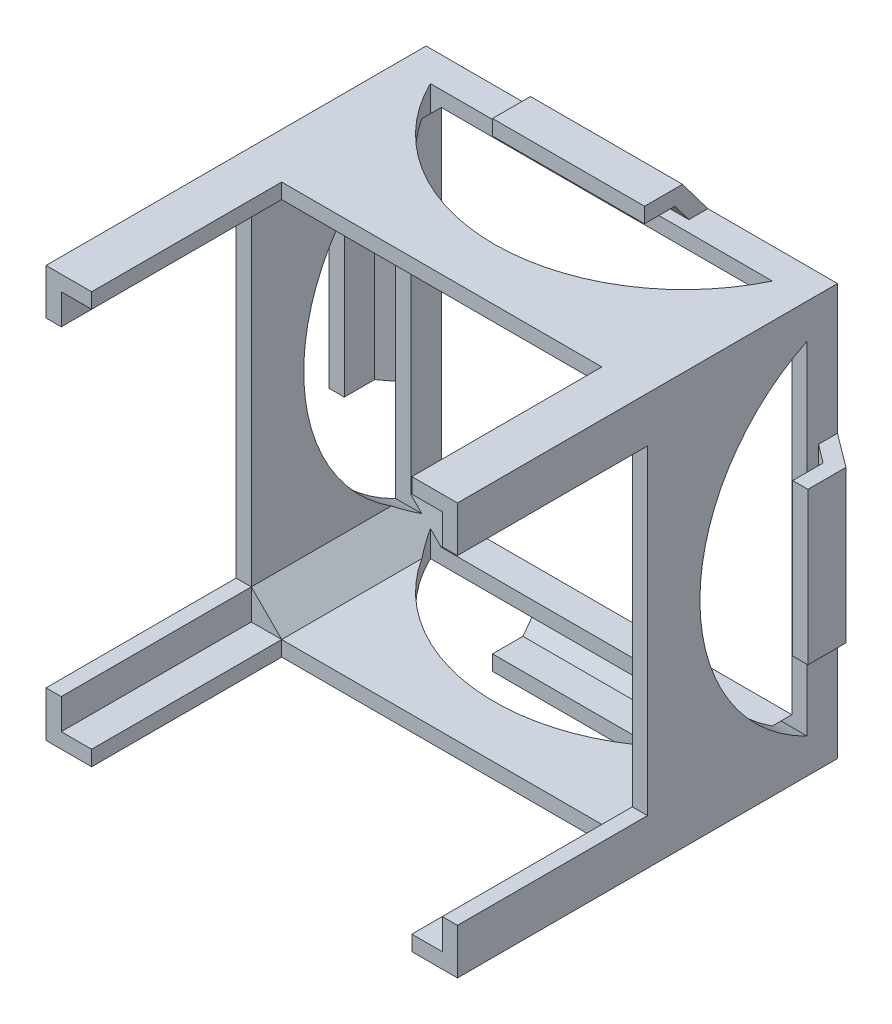
SolidWorks part; units mm, degrees
ref_plane "Front Plane" through (0, 0, 0) normal (0, 0, 1) x (1, 0, 0)
ref_plane "Top Plane" through (0, 0, 0) normal (0, 1, 0) x (1, 0, 0)
ref_plane "Right Plane" through (0, 0, 0) normal (1, 0, 0) x (0, 0, -1)
sketch "Sketch1" plane through (0, 0, 0) normal (0, 0, 1) x (1, 0, 0)
  line L1 (-50.125, -50.125) -> (50.125, -50.125)
  line L2 (-50.125, -50.125) -> (-50.125, 50.125)
  line L3 (-50.125, 50.125) -> (50.125, 50.125)
  line L4 (50.125, -50.125) -> (50.125, 50.125)
  line L5 (-50.125, -50.125) -> (50.125, 50.125) construction
  line L6 (-50.125, 50.125) -> (50.125, -50.125) construction
  line L7 (-54.125, -54.125) -> (54.125, -54.125)
  line L8 (-54.125, -54.125) -> (-54.125, 54.125)
  line L9 (-54.125, 54.125) -> (54.125, 54.125)
  line L10 (54.125, -54.125) -> (54.125, 54.125)
  line L11 (-54.125, -54.125) -> (54.125, 54.125) construction
  line L12 (-54.125, 54.125) -> (54.125, -54.125) construction
  point P0 (0, 0)
  point P6 (0, 0)
  dimension "D1" = 100.25
  dimension "D2" = 4
extrude "Base" add sketch "Sketch1" along normal blind 50
chamfer "Chamfer" distance 8 angle 45 4 edges at (-50.125, -50.125, 25) (50.125, -50.125, 25) (50.125, 50.125, 25) (-50.125, 50.125, 25)
sketch "Sketch3" plane through (0, 0, 0) normal (0, 1, 0) x (1, 0, 0)
  line L0 (54.125, 0) -> (63, -6.6563)
  line L1 (54.125, -50) -> (54.125, 0) construction
  line L2 (63, -6.6563) -> (63, -16.6562)
  line L3 (63, -16.6562) -> (59, -16.6562)
  line L4 (59, -16.6562) -> (59, -8.6562)
  line L5 (59, -8.6562) -> (54.125, -5)
  line L6 (59, -8.6562) -> (61.4, -5.4563) construction
  line L7 (54.125, -5) -> (54.125, 0)
  dimension "D4" = 63
  dimension "D3" = 10
extrude "Wall-Brace" add sketch "Sketch3" along normal blind 20 and the other way blind 20
ref_axis "Vertical-Axis" through (0, 0, -5) along (0, 0, 1)
pattern_circular "Wall-Brace-Pattern" count 4 over 360 about axis through (0, 0, -5) along (0, 0, 1) of "Wall-Brace"
sketch "Sketch4" plane through (0, 0, 50) normal (0, 0, 1) x (1, 0, 0)
  line L0 (-50.125, 42.125) -> (-54.125, 42.125)
  line L1 (-54.125, 54.125) -> (-54.125, -54.125) construction
  line L2 (-54.125, 42.125) -> (-54.125, 54.125)
  line L3 (-54.125, 54.125) -> (-42.125, 54.125)
  line L4 (54.125, 54.125) -> (-54.125, 54.125) construction
  line L5 (-42.125, 54.125) -> (-42.125, 50.125)
  line L6 (-42.125, 50.125) -> (-50.125, 50.125)
  line L7 (-50.125, 50.125) -> (-50.125, 42.125)
extrude "Lattice-Support-Arm" add sketch "Sketch4" along normal blind 50
mirror "Lattice-Support-Arm-Mirror" about plane through (0, 0, 0) normal (1, 0, 0) of "Lattice-Support-Arm" second plane through (0, 0, 0) second plane normal (0, 1, 0)
sketch "Sketch5" plane through (54.125, 0, 0) normal (-1, 0, 0) x (0, 0, 1)
  line L9 (8, 45) -> (8, -45)
  line L11 (0, 54.125) -> (0, 20) construction
  line L12 (8, -54.125) -> (8, 54.125) construction
  line L14 (100, -54.125) -> (0, -54.125) construction
  line L15 (100, 54.125) -> (0, 54.125) construction
  arc A3 (8, 45) -> (8, -45) centre (-13.7945, 0) cw
  point P13 (8, 0)
  point P16 (8, 0)
  dimension "D2" = 50
  dimension "D1" = 90
  dimension "D3" = 8
extrude "Arches-1" cut sketch "Sketch5" along normal up to surface (108.25 mm away) up to face at (-54.125, 0, 42.5)
sketch "Sketch6" plane through (0, 54.125, 0) normal (0, 1, 0) x (1, 0, 0)
  line L0 (-45, -8) -> (45, -8)
  line L1 (-54.125, -8) -> (54.125, -8) construction
  line L2 (-54.125, -100) -> (-54.125, 0) construction
  line L3 (54.125, -100) -> (54.125, 0) construction
  line L4 (-20, 0) -> (-54.125, 0) construction
  arc A0 (45, -8) -> (-45, -8) centre (0, 13.7945) cw
  point P4 (0, -8)
  point P10 (0, -8)
  dimension "D2" = 50
  dimension "D1" = 90
  dimension "D3" = 8
extrude "Arches-2" cut sketch "Sketch6" against normal up to surface (108.25 mm away) up to face at (0, -54.125, 42.5)
equation "\"D1@Sketch1\" = \"block-base\" + \"block-tolerance\""
equation "\"D2@Sketch1\" = \"frame-thickness\""
equation "\"D1@Chamfer\" = \"frame-thickness\" * 2"
equation "\"D1@Sketch3\" = \"frame-thickness\""
equation "\"D4@Sketch3\"=\"box-size\"/2"
equation "\"D1@Wall-Brace\" = 20mm"
equation "\"D2@Wall-Brace\" = 20mm"
equation "\"box-size\"= 126mm"
equation "\"block-base\"= 100mm"
equation "\"block-height\"= 50mm"
equation "\"hole-separation\"= 50mm"
equation "\"frame-thickness\"= 4mm"
equation "\"block-tolerance\"= 0.25mm"
equation "\"frame-height\"= 50mm"
equation "\"D1@Base\" = \"frame-height\""
equation "\"D1@Lattice-Support-Arm\" = \"block-height\""
equation "\"window-radius\"= 50mm"
equation "\"window-width\"= 90mm"
equation "\"D2@Sketch5\"=\"window-radius\""
equation "\"D1@Sketch5\"=\"window-width\""
equation "\"D1@Sketch6\"=\"window-width\""
equation "\"D2@Sketch6\"=\"window-radius\""
equation "\"D3@Sketch6\"=\"frame-thickness\"*2"
equation "\"D3@Sketch5\"=\"frame-thickness\"*2"
